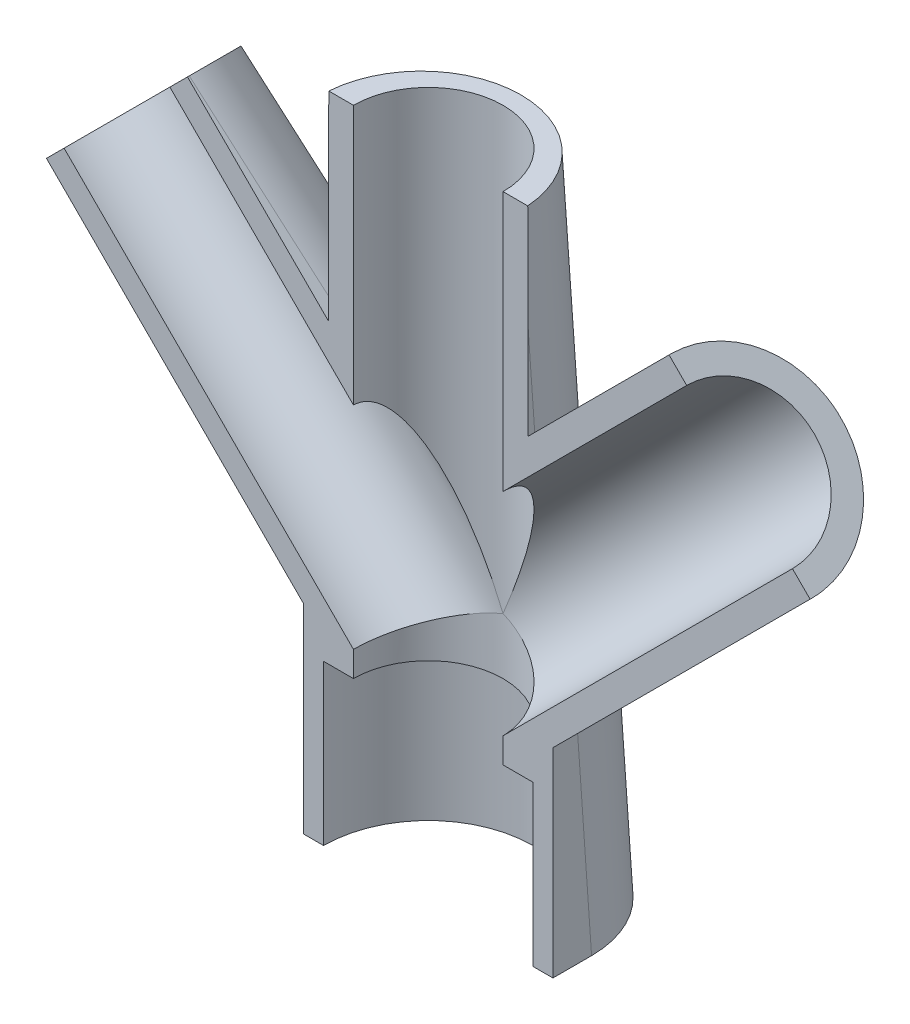
SolidWorks part; units mm, degrees
ref_plane "Спереди" through (0, 0, 0) normal (0, 0, 1) x (1, 0, 0)
ref_plane "Сверху" through (0, 0, 0) normal (0, 1, 0) x (1, 0, 0)
ref_plane "Справа" through (0, 0, 0) normal (1, 0, 0) x (0, 0, -1)
sketch "Эскиз3" plane through (0, 0, 0) normal (0, 0, 1) x (1, 0, 0)
  line L1 (0, -50) -> (0, 50) construction
  line L3 (-6.25, 0) -> (-19.1421, 12.8921)
  line L4 (-19.1421, 12.8921) -> (-12.0711, 19.9632)
  line L5 (-12.0711, 19.9632) -> (-5, 12.8921)
  line L6 (-5, 12.8921) -> (-5, 22.8921)
  line L7 (-5, 22.8921) -> (5, 22.8921)
  line L8 (0, 22.8921) -> (0, 0) construction
  line L9 (5, 12.8921) -> (5, 22.8921)
  line L10 (12.0711, 19.9632) -> (5, 12.8921)
  line L11 (19.1421, 12.8921) -> (12.0711, 19.9632)
  line L12 (6.25, 0) -> (19.1421, 12.8921)
  line L17 (-6.25, 0) -> (-6.25, -10)
  line L18 (-6.25, -10) -> (6.25, -10)
  line L19 (6.25, 0) -> (6.25, -10)
  dimension "D1" = 12.5
  dimension "D2" = 10
  dimension "D3" = 10
  dimension "D4" = 45
  dimension "D5" = 10
extrude "Основа тройника" add sketch "Эскиз3" along normal blind 12.5
sketch "Эскиз4" plane through (0, 22.8921, 0) normal (0, 1, 0) x (-1, 0, 0)
  line L3 (5, 12.5) -> (5, 0) construction
  line L5 (-5, 12.5) -> (5, 12.5) construction
  circle A0 centre (0, 6.25) radius 3.75
  point P2 (0, 0)
  point P4 (0, 4.3932)
  point P5 (0, 0)
  point P7 (0, 0)
  point P8 (5, 6.25)
  point P11 (0, 0)
  point P14 (0, 12.5)
  dimension "D1" = 7.5
extrude "Центральный вырез под гофру" cut sketch "Эскиз4" against normal through all
sketch "Эскиз5" plane through (-16.0171, 16.0171, 0) normal (-0.7071, 0.7071, 0) x (0, 0, 1)
  line L0 (6.25, 16.1872) -> (6.25, -7.0711) construction
  line L1 (12.5, 5.5806) -> (12.5, -4.4194) construction
  circle A0 centre (6.25, 0.5806) radius 3.75
  point P7 (12.5, 0.5806)
  dimension "D1" = 7.5
extrude "Боковой вырез под гофру" cut sketch "Эскиз5" against normal up to next
mirror "Зеркальное отражение1" about plane through (0, 0, 0) normal (1, 0, 0) of "Боковой вырез под гофру"
sketch "Эскиз9" plane through (0, -10, 0) normal (0, -1, 0) x (1, 0, 0)
  circle A0 centre (0, 6.25) radius 5.25
  dimension "D1" = 10.5
extrude "Под толстую гофру" cut sketch "Эскиз9" against normal blind 8
draft "Уклон2" type of draft neutral plane draft angle 4 neutral plane "Сверху" faces to draft 2 face at (0, 9.7733, 0) face at (0, 9.7733, 12.5) neutral plane through (0, 0, 0) neutral plane normal (0, 1, 0) parameters "D1"=4
fillet "Скругление8" radius 5 16 edges at (8.5355, 16.4277, 1.1487) (5, 17.8921, 1.2511) (-5, 17.8921, 1.2511) (-8.5355, 16.4277, 1.1487) (-12.6961, 6.4461, 0.4508) (-6.25, -5, -0.3496) (6.25, -5, -0.3496) (12.6961, 6.4461, 0.4508) (-6.25, -5, 12.8496) (6.25, -5, 12.8496) (12.6961, 6.4461, 12.0492) (8.5355, 16.4277, 11.3513) (5, 17.8921, 11.2489) (-5, 17.8921, 11.2489) (-8.5355, 16.4277, 11.3513) (-12.6961, 6.4461, 12.0492)
sketch "Эскиз10" plane through (0, -10, 0) normal (0, -1, 0) x (1, 0, 0)
  line L0 (0, 6.25) -> (15.6066, 6.25) construction
  line L1 (-24.7446, 14.8445) -> (24.293, 14.8445)
  line L2 (-24.7446, 14.8445) -> (-24.7446, 6.25)
  line L3 (-24.7446, 6.25) -> (24.293, 6.25)
  line L4 (24.293, 14.8445) -> (24.293, 6.25)
extrude "Вырез-Вытянуть3" cut sketch "Эскиз10" against normal through all
